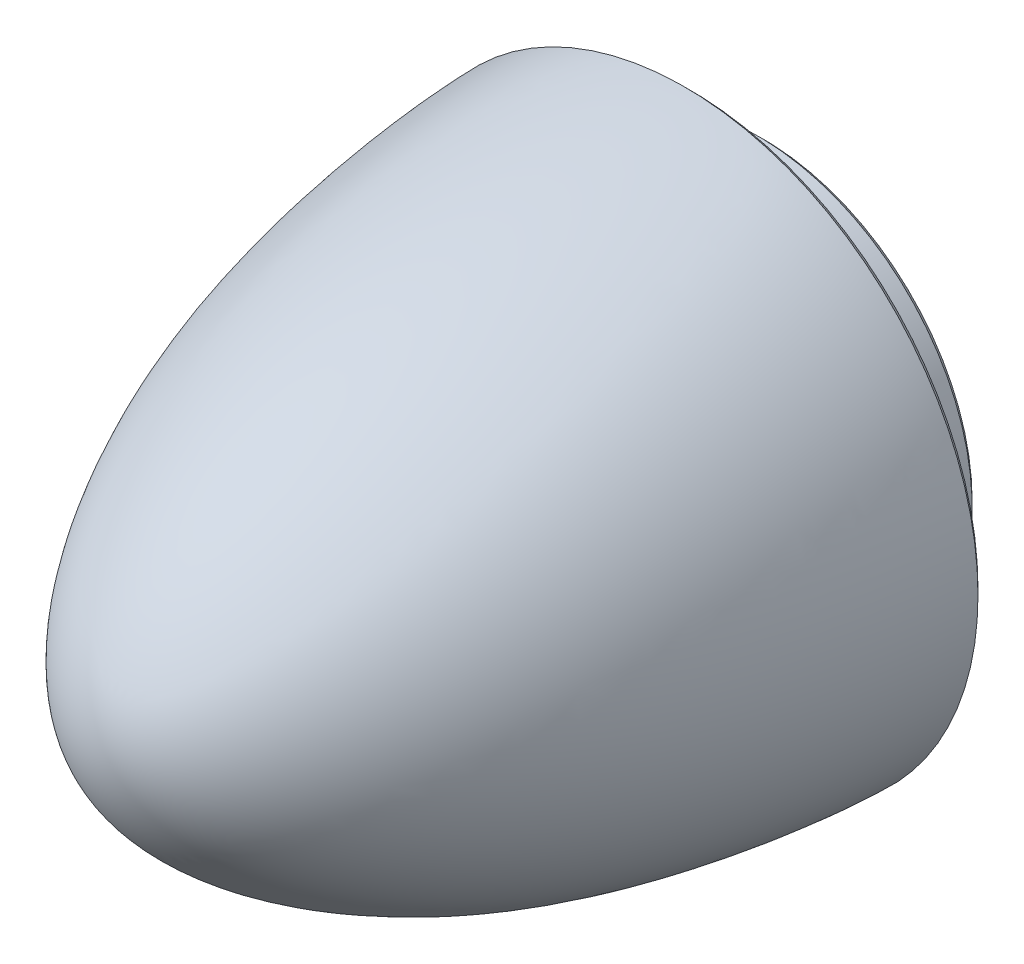
SolidWorks part; units mm, degrees
ref_plane "Front Plane" through (0, 0, 0) normal (0, 0, 1) x (1, 0, 0)
ref_plane "Top Plane" through (0, 0, 0) normal (0, 1, 0) x (1, 0, 0)
ref_plane "Right Plane" through (0, 0, 0) normal (1, 0, 0) x (0, 0, -1)
sketch "Sketch2" plane through (0, 0, 0.1005) normal (0, 1, 0) x (1, 0, 0)
  line L0 (0, 0) -> (0, 25.4)
  line L1 (0, 12.7) -> (10.6627, 12.7) construction
  line L3 (0, 0) -> (0, 25.4) construction
  line L7 (0, 25.4) -> (12.7, 25.4)
  spline S1 degree 3 poles (0, 0) (4.2518, -0.0002) (11.6078, 10.0817) (12.7, 23.2927) (12.7, 25.4) knots 0.5 0.5 0.5 0.5 0.789003 1 1 1 1
  point P13 (10.6627, 12.7)
revolve "Revolve5" add sketch "Sketch2" angle 360 about L3
sketch "Sketch3" plane through (0, 0, -25.2995) normal (0, 0, -1) x (-1, 0, 0)
  circle A0 centre (0, 0) radius 9.271
  dimension "D1" = 18.542
extrude "Boss-Extrude1" add sketch "Sketch3" along normal blind 3.175
fillet "Fillet1" radius 0.254 1 edges at (-9.271, 0, -25.2995)
chamfer "Chamfer1" distance 0.254 angle 45 2 edges at (-9.271, 0, -28.4745) (12.7, 0, -25.2995)
